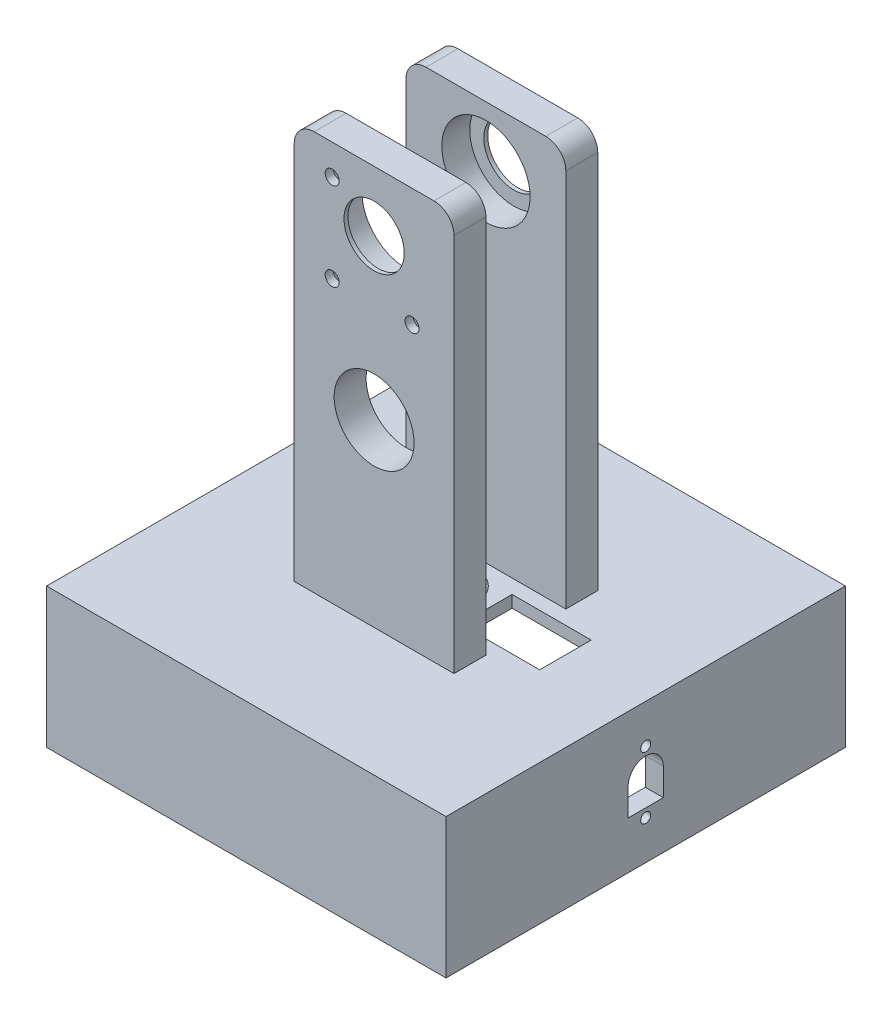
SolidWorks part; units mm, degrees
ref_plane "Front Plane" through (0, 0, 0) normal (0, 0, 1) x (1, 0, 0)
ref_plane "Top Plane" through (0, 0, 0) normal (0, 1, 0) x (1, 0, 0)
ref_plane "Right Plane" through (0, 0, 0) normal (1, 0, 0) x (0, 0, -1)
sketch "Sketch1" plane through (0, 0, 0) normal (0, 1, 0) x (1, 0, 0)
  line L1 (-50, -50) -> (50, -50)
  line L2 (-50, -50) -> (-50, 50)
  line L3 (-50, 50) -> (50, 50)
  line L4 (50, -50) -> (50, 50)
  line L5 (-50, -50) -> (50, 50) construction
  line L6 (-50, 50) -> (50, -50) construction
  point P0 (0, 0)
  dimension "D1" = 100
  dimension "D2" = 100
extrude "Boss-Extrude1" add sketch "Sketch1" along normal blind 35
sketch "Sketch2" plane through (0, 0, 0) normal (0, -1, 0) x (1, 0, 0)
  line L1 (-45.5, -45.5) -> (45.5, -45.5)
  line L2 (-45.5, -45.5) -> (-45.5, 45.5)
  line L3 (-45.5, 45.5) -> (45.5, 45.5)
  line L4 (45.5, -45.5) -> (45.5, 45.5)
  line L5 (-45.5, -45.5) -> (45.5, 45.5) construction
  line L6 (-45.5, 45.5) -> (45.5, -45.5) construction
  point P0 (0, 0)
  dimension "D1" = 91
  dimension "D2" = 91
extrude "Cut-Extrude1" cut sketch "Sketch2" against normal blind 32
sketch "Sketch3" plane through (50, 0, 0) normal (1, 0, 0) x (0, 0, -1)
  line L0 (0, 0) -> (0, 35) construction
  line L1 (-50, 35) -> (50, 35) construction
  line L2 (0, 17.5) -> (0, 7.5) construction
  line L3 (-4.4, 11.9) -> (4.4, 11.9)
  line L4 (-4.4, 11.9) -> (-4.4, 18.75)
  line L9 (4.4, 11.9) -> (4.4, 18.75)
  line L10 (0, 17.5) -> (0, 25.25) construction
  line L11 (0, 17.5) -> (3, 17.5) construction
  arc A1 (-4.4, 18.75) -> (4.4, 18.75) centre (0, 18.75) cw
  circle A2 centre (0, 25.25) radius 1.25
  circle A3 centre (0, 9.75) radius 1.25
  dimension "D7" = 7.75
  dimension "D8" = 2.5
  dimension "D1" = 10
  dimension "D2" = 4.4
  dimension "D3" = 8.8
  dimension "D4" = 6.85
  dimension "D5" = 4.4
  dimension "D6" = 6.85
  dimension "D9" = 3
extrude "Cut-Extrude3" cut sketch "Sketch3" against normal up to next
sketch "Sketch5" plane through (0, 35, 0) normal (0, 1, 0) x (1, 0, 0)
  line L0 (50, 0) -> (20, 0) construction
  line L1 (50, -50) -> (50, 50) construction
  line L3 (29.9, -6.45) -> (10.1, -6.45)
  line L4 (29.9, -6.45) -> (29.9, 6.45)
  line L5 (29.9, 6.45) -> (10.1, 6.45)
  line L6 (10.1, -6.45) -> (10.1, 6.45)
  line L7 (29.9, -6.45) -> (10.1, 6.45) construction
  line L8 (29.9, 6.45) -> (10.1, -6.45) construction
  dimension "D1" = 30
  dimension "D2" = 19.8
  dimension "D3" = 12.9
extrude "Cut-Extrude4" cut sketch "Sketch5" against normal up to next
sketch "Sketch6" plane through (0, 35, 0) normal (0, 1, 0) x (1, 0, 0)
  line L0 (0, 0) -> (0, -10) construction
  line L1 (20, -10) -> (-20, -10)
  line L2 (-20, -10) -> (-20, -18)
  line L3 (20, -10) -> (20, -18)
  line L4 (20, -18) -> (-20, -18)
  point P6 (0, -10)
  dimension "D1" = 10
  dimension "D2" = 40
  dimension "D3" = 8
extrude "Boss-Extrude2" add sketch "Sketch6" along normal blind 100
sketch "Sketch7" plane through (0, 0, 10) normal (0, 0, -1) x (-1, 0, 0)
  line L0 (0, 135) -> (0, 119.9) construction
  line L1 (-20, 135) -> (20, 135) construction
  circle A0 centre (0, 119.9) radius 11.05
  dimension "D2" = 22.1
  dimension "D1" = 15.1
extrude "Cut-Extrude5" cut sketch "Sketch7" against normal blind 7
sketch "Sketch8" plane through (0, 0, 18) normal (0, 0, 1) x (1, 0, 0)
  line L0 (0, 135) -> (0, 119.9) construction
  line L1 (-20, 135) -> (20, 135) construction
  circle A0 centre (0, 119.9) radius 7.55
  dimension "D2" = 15.1
  dimension "D1" = 15.1
extrude "Cut-Extrude6" cut sketch "Sketch8" against normal up to next
fillet "Fillet1" radius 5 2 edges at (-20, 135, 14) (20, 135, 14)
mirror "Mirror2" about plane through (0, 0, 0) normal (0, 0, 1) of "Fillet1", "Cut-Extrude6", "Cut-Extrude5", "Boss-Extrude2"
sketch "Sketch9" plane through (0, 35, 0) normal (0, 1, 0) x (1, 0, 0)
  circle A0 centre (0, 0) radius 7.5
  dimension "D1" = 15
extrude "Cut-Extrude7" cut sketch "Sketch9" against normal up to next
sketch "Sketch12" plane through (0, 0, 18) normal (0, 0, 1) x (1, 0, 0)
  line L0 (0, 35) -> (0, 80) construction
  line L1 (-20, 35) -> (20, 35) construction
  circle A0 centre (0, 80) radius 10
  dimension "D2" = 20
  dimension "D1" = 45
extrude "Cut-Extrude10" cut sketch "Sketch12" against normal up to next
sketch "Sketch13" plane through (0, 0, 18) normal (0, 0, 1) x (1, 0, 0)
  line L0 (0, 119.9) -> (0, 102.9) construction
  line L1 (0, 102.9) -> (-13, 102.9) construction
  line L2 (-13, 102.9) -> (12, 102.9) construction
  line L3 (-13, 102.9) -> (-13, 129.9) construction
  line L4 (-13, 129.9) -> (12, 129.9) construction
  line L5 (12, 129.9) -> (12, 102.9) construction
  line L6 (-10.5, 102.9) -> (-10.5, 105.4) construction
  line L7 (-10.5, 105.4) -> (-13, 105.4) construction
  line L8 (-13, 116.4) -> (12, 116.4) construction
  line L9 (-0.5, 129.9) -> (-0.5, 102.9) construction
  circle A0 centre (-10.5, 105.4) radius 1.75
  circle A1 centre (-10.5, 127.4) radius 1.75
  circle A2 centre (9.5, 105.4) radius 1.75
  dimension "D7" = 3.5
  dimension "D1" = 17
  dimension "D2" = 13
  dimension "D3" = 27
  dimension "D4" = 25
  dimension "D5" = 2.5
  dimension "D6" = 2.5
extrude "Cut-Extrude11" cut sketch "Sketch13" against normal up to next
sketch "Sketch14" plane through (0, 0, 10) normal (0, 0, -1) x (-1, 0, 0)
  line L0 (10.5, 105.4) -> (-9.5, 105.4) construction
  line L1 (10.5, 105.4) -> (10.5, 127.4) construction
  line L2 (0.5, 105.4) -> (0.5, 107.4) construction
  line L3 (10.5, 116.4) -> (8.5, 116.4) construction
  line L4 (-11.1743, 108.3) -> (-7.8257, 108.3)
  line L5 (13.8486, 105.4) -> (12.1743, 108.3)
  line L6 (12.1743, 108.3) -> (8.8257, 108.3)
  line L7 (8.8257, 108.3) -> (7.1514, 105.4)
  line L8 (7.1514, 105.4) -> (8.8257, 102.5)
  line L9 (8.8257, 102.5) -> (12.1743, 102.5)
  line L10 (12.1743, 102.5) -> (13.8486, 105.4)
  line L11 (-12.8486, 105.4) -> (-11.1743, 108.3)
  line L12 (-11.1743, 102.5) -> (-12.8486, 105.4)
  line L13 (-7.8257, 102.5) -> (-11.1743, 102.5)
  line L14 (-6.1514, 105.4) -> (-7.8257, 102.5)
  line L15 (-7.8257, 108.3) -> (-6.1514, 105.4)
  line L16 (7.1514, 127.4) -> (8.8257, 130.3)
  line L17 (8.8257, 130.3) -> (12.1743, 130.3)
  line L18 (12.1743, 130.3) -> (13.8486, 127.4)
  line L19 (13.8486, 127.4) -> (12.1743, 124.5)
  line L20 (12.1743, 124.5) -> (8.8257, 124.5)
  line L21 (8.8257, 124.5) -> (7.1514, 127.4)
  circle A0 centre (10.5, 105.4) radius 2.9 construction
  dimension "D3" = 5.8
  dimension "D1" = 2
  dimension "D2" = 2
extrude "Cut-Extrude12" cut sketch "Sketch14" against normal blind 6
